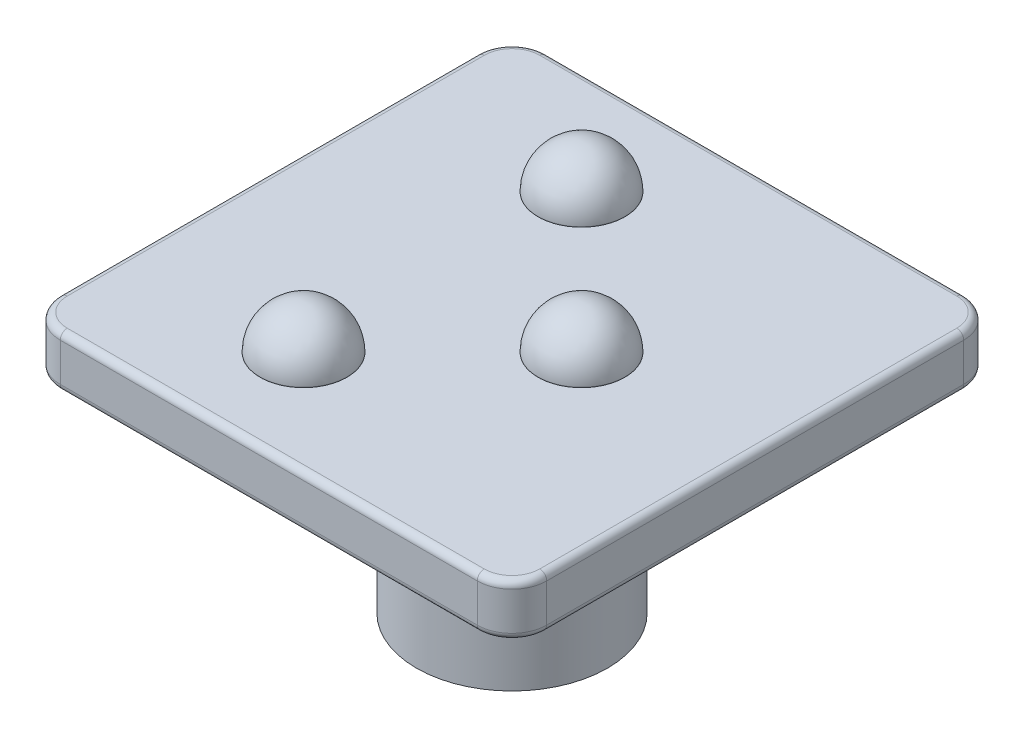
SolidWorks part; units mm, degrees
ref_plane "Front Plane" through (0, 0, 0) normal (0, 0, 1) x (1, 0, 0)
ref_plane "Top Plane" through (0, 0, 0) normal (0, 1, 0) x (1, 0, 0)
ref_plane "Right Plane" through (0, 0, 0) normal (1, 0, 0) x (0, 0, -1)
sketch "Sketch1" plane through (0, 0, 0) normal (0, 1, 0) x (1, 0, 0)
  line L1 (-7.3247, 4.3967) -> (4.6753, 4.3967)
  line L2 (-8.3247, 3.3967) -> (-8.3247, -8.6033)
  line L3 (-7.3247, -9.6033) -> (4.6753, -9.6033)
  line L4 (5.6753, 3.3967) -> (5.6753, -8.6033)
  arc A0 (-8.3247, -8.6033) -> (-7.3247, -9.6033) centre (-7.3247, -8.6033) ccw
  arc A1 (4.6753, -9.6033) -> (5.6753, -8.6033) centre (4.6753, -8.6033) ccw
  arc A2 (4.6753, 4.3967) -> (5.6753, 3.3967) centre (4.6753, 3.3967) cw
  arc A3 (-7.3247, 4.3967) -> (-8.3247, 3.3967) centre (-7.3247, 3.3967) ccw
  point P8 (5.6753, -9.6033)
  point P11 (5.6753, 4.3967)
  point P14 (-8.3247, 4.3967)
  dimension "D3" = 1
  dimension "D1" = 14
  dimension "D2" = 14
extrude "Boss-Extrude1" add sketch "Sketch1" along normal blind 1.5
sketch "Sketch2" plane through (0, 0, 0) normal (0, -1, 0) x (1, 0, 0)
  line L0 (-7.3247, 9.6033) -> (4.6753, 9.6033) construction
  line L1 (5.6753, 8.6033) -> (5.6753, -3.3967) construction
  line L2 (-1.3247, -4.3967) -> (-1.3247, 9.6033) construction
  line L3 (-8.3247, 2.6033) -> (5.6753, 2.6033) construction
  line L4 (-8.3247, -3.3967) -> (-8.3247, 8.6033) construction
  circle A0 centre (-1.3247, 2.6033) radius 2.75
  dimension "D1" = 7
  dimension "D2" = 7
extrude "Boss-Extrude2" add sketch "Sketch2" along normal blind 6
sketch "Sketch3" plane through (0, -6, 0) normal (0, -1, 0) x (1, 0, 0)
  line L0 (-1.3247, 5.3533) -> (-1.3247, -0.1467) construction
  line L1 (-3.3247, 3.1533) -> (0.6753, 3.1533)
  line L2 (-3.3247, 3.1533) -> (-3.3247, 2.0533)
  line L3 (-3.3247, 2.0533) -> (0.6753, 2.0533)
  line L4 (0.6753, 3.1533) -> (0.6753, 2.0533)
  line L5 (-1.8747, 4.6033) -> (-0.7747, 4.6033)
  line L6 (-1.8747, 4.6033) -> (-1.8747, 0.6033)
  line L7 (-1.8747, 0.6033) -> (-0.7747, 0.6033)
  line L8 (-0.7747, 4.6033) -> (-0.7747, 0.6033)
  line L9 (-4.0747, 2.6033) -> (1.4253, 2.6033) construction
  circle A3 centre (-1.3247, 2.6033) radius 2.75 construction
  circle A4 centre (-1.3247, 2.6033) radius 2.75 construction
  dimension "D7" = 0.55
  dimension "D1" = 4
  dimension "D2" = 1.1
  dimension "D3" = 1.1
  dimension "D4" = 4
  dimension "D8" = 0.55
extrude "Cut-Extrude1" cut sketch "Sketch3" against normal blind 6 contours L8 L5 L6 L1 | L1 L8 L3 L4 | L8 L1 L6 L3 | L6 L1 L2 L3 | L8 L3 L6 L7 region at (-2.5997, -6, 2.6033) region at (-1.3247, -6, 3.8783) region at (-1.3247, -6, 2.6033) region at (-0.0497, -6, 2.6033) region at (-1.3247, -6, 1.3283)
chamfer "Chamfer1" distance 0.3 angle 45 12 edges at (-1.3247, -6, 0.6033) (-1.8747, -6, 1.3283) (-2.5997, -6, 2.0533) (-3.3247, -6, 2.6033) (-2.5997, -6, 3.1533) (-0.7747, -6, 1.3283) (-0.0497, -6, 2.0533) (0.6753, -6, 2.6033) (-0.0497, -6, 3.1533) (-0.7747, -6, 3.8783) (-1.3247, -6, 4.6033) (-1.8747, -6, 3.8783)
fillet "Fillet1" radius 1 1 edges at (-1.3247, 0, -0.1467)
sketch "Sketch4" plane through (0, 1.5, 0) normal (0, 1, 0) x (1, 0, 0)
  line L0 (-1.3247, 4.3967) -> (-1.3247, -9.6033) construction
  line L1 (4.6753, 4.3967) -> (-7.3247, 4.3967) construction
  line L2 (-7.3247, -9.6033) -> (4.6753, -9.6033) construction
  line L3 (5.6753, -2.6033) -> (-8.3247, -2.6033) construction
  line L4 (-8.3247, 3.3967) -> (-8.3247, -8.6033) construction
  line L5 (5.6753, -8.6033) -> (5.6753, 3.3967) construction
  line L6 (-3.3247, 4.3967) -> (-3.3247, -9.6033) construction
  line L7 (0.6753, 4.3967) -> (0.6753, -9.6033) construction
  line L8 (-8.3247, 1.3967) -> (5.6753, 1.3967) construction
  line L9 (5.6753, -6.6033) -> (-8.3247, -6.6033) construction
  circle A0 centre (-3.3247, 1.3967) radius 1.25
  circle A1 centre (0.6753, -2.6033) radius 1.25
  circle A3 centre (-3.3247, -6.6033) radius 1.25
  dimension "D1" = 4
  dimension "D2" = 4
  dimension "D3" = 2
  dimension "D4" = 2
extrude "Boss-Extrude3" add sketch "Sketch4" along normal blind 0.01
dome "Dome1" faces to dome 1 distance 1.25 reverse direction no elliptical dome no face at (-3.3247, 1.51, -0.1467) parameters "D1"=1.25
dome "Dome4" faces to dome 1 distance 1.25 reverse direction no elliptical dome no face at (0.6753, 1.51, 3.8533) parameters "D1"=1.25
dome "Dome5" faces to dome 1 distance 1.25 reverse direction no elliptical dome no face at (-3.3247, 1.51, 7.8533) parameters "D1"=1.25
fillet "Fillet3" radius 0.2 16 edges at (5.3824, 1.5, -4.1038) (5.6753, 1.5, 2.6033) (5.3824, 1.5, 9.3104) (-1.3247, 1.5, 9.6033) (-8.0318, 1.5, 9.3104) (-8.0318, 1.5, -4.1038) (-8.3247, 1.5, 2.6033) (-1.3247, 1.5, -4.3967) (5.3824, 0, 9.3104) (5.6753, 0, 2.6033) (5.3824, 0, -4.1038) (-1.3247, 0, -4.3967) (-8.0318, 0, -4.1038) (-8.3247, 0, 2.6033) (-8.0318, 0, 9.3104) (-1.3247, 0, 9.6033)
